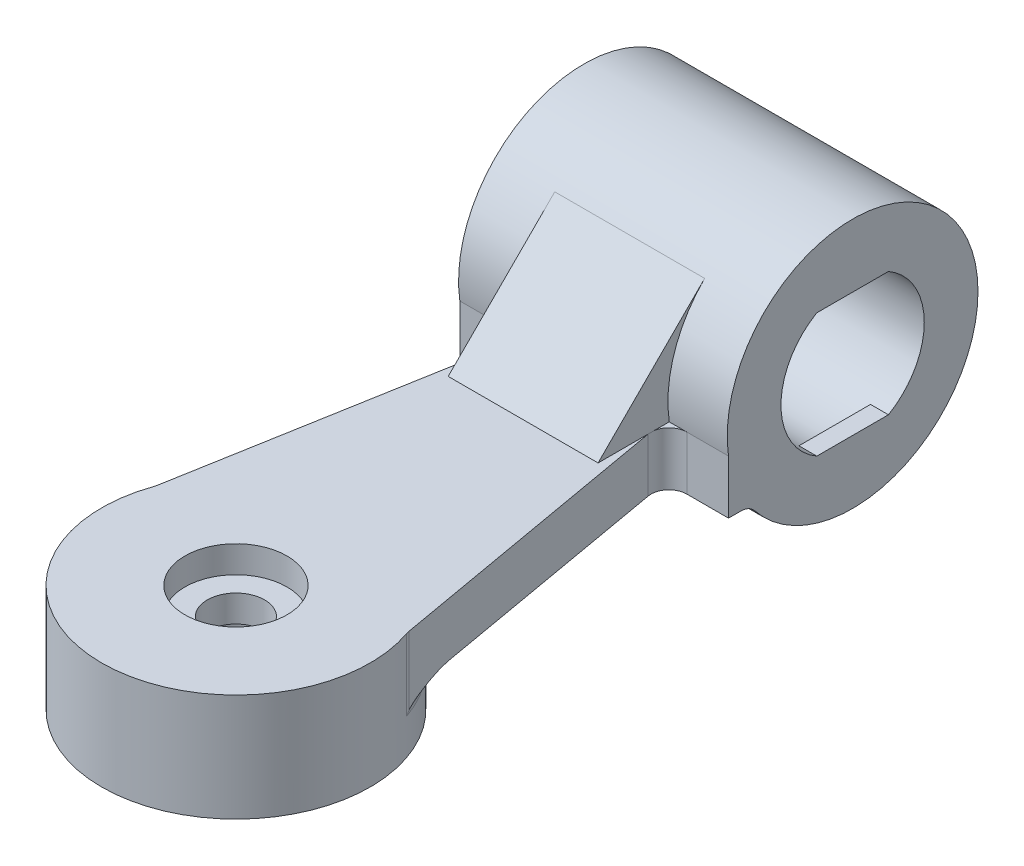
SolidWorks part; units mm, degrees
ref_plane "Front Plane" through (0, 0, 0) normal (0, 0, 1) x (1, 0, 0)
ref_plane "Top Plane" through (0, 0, 0) normal (0, 1, 0) x (1, 0, 0)
ref_plane "Right Plane" through (0, 0, 0) normal (1, 0, 0) x (0, 0, -1)
sketch "Sketch2" plane through (0, 0, 0) normal (0, 1, 0) x (1, 0, 0)
  circle A0 centre (0, 0) radius 7.5
  dimension "D1" = 15
extrude "Boss-Extrude2" add sketch "Sketch2" along normal blind 6
sketch "Sketch3" plane through (0, 6, 0) normal (0, 1, 0) x (1, 0, 0)
  line L0 (-7.0477, 2.5652) -> (-3.9735, 20)
  line L1 (3.9823, 20) -> (7.065, 2.5172)
  line L2 (-3.9735, 20) -> (3.9823, 20)
  circle A0 centre (0, 0) radius 7.5 construction
  arc A1 (7.065, 2.5172) -> (-7.0477, 2.5652) centre (0, 0) ccw
  point P3 (3.9735, 20)
  point P5 (7.065, 2.5652)
  dimension "D1" = 20
  dimension "D2" = 100
  dimension "D3" = 100
extrude "Boss-Extrude3" add sketch "Sketch3" against normal offset from surface (3 mm away) 3 up to face at (0, 0, 7.5)
sketch "Sketch6" plane through (0, 0, 0) normal (0, -1, 0) x (1, 0, 0)
  circle A0 centre (0, 0) radius 2.85
  dimension "D1" = 5.7
extrude "Cut-Extrude1" cut sketch "Sketch6" against normal up to surface (6 mm away) up to face at (-0.002, 6, -8.7603)
sketch "Sketch8" plane through (0, 0, 0) normal (1, 0, 0) x (0, 0, -1)
  line L0 (-7.5, 0) -> (7.5, 0) construction
  circle A0 centre (26.9282, 7) radius 4
  circle A1 centre (26.9282, 7) radius 7
  point P0 (27.3813, 7.7366)
  dimension "D1" = 8
  dimension "D2" = 3
extrude "Boss-Extrude4" add sketch "Sketch8" along normal blind 7.5 and the other way blind 7.5 separate body
sketch "Sketch9" plane through (0, 0, 0) normal (1, 0, 0) x (0, 0, -1)
  line L0 (20, 3) -> (20, 6) construction
  line L1 (20, 3) -> (20, 6)
  line L2 (20, 3) -> (21.1836, 3)
  circle A0 centre (26.9282, 7) radius 7 construction
  arc A1 (20, 6) -> (21.1836, 3) centre (26.9282, 7) ccw
extrude "Boss-Extrude5" add sketch "Sketch9" along normal blind 7.5 and the other way blind 7.5
ref_plane "Plane1" through (0, 3, 0) normal (0, 1, 0) x (1, 0, 0)
sketch "Sketch11" plane through (0, 3, 0) normal (0, 1, 0) x (1, 0, 0)
  circle A0 centre (0, 0) radius 1.6
  circle A1 centre (0, 0) radius 2.85 construction
  circle A2 centre (0, 0) radius 2.85
  dimension "D1" = 3.2
extrude "Boss-Extrude6" add sketch "Sketch11" along normal blind 1.5
fillet "Fillet15" radius 1 2 edges at (3.9823, 4.5, -20) (-3.9735, 4.5, -20)
fillet "Fillet16" radius 1 1 edges at (0, 3, -21.1836)
fillet "Fillet23" radius 1 1 edges at (0.0255, 3, -7.5)
fillet "Fillet24" radius 1 2 edges at (7.065, 4, -2.5172) (-7.0477, 4, -2.5652)
sketch "Sketch12" plane through (7.5, 0, 0) normal (1, 0, 0) x (0, 0, -1)
  line L0 (24.9282, 3.5359) -> (28.9282, 3.5359)
  line L1 (24.9282, 10.4641) -> (28.9282, 10.4641)
  circle A0 centre (26.9282, 7) radius 4 construction
  arc A1 (24.9282, 3.5359) -> (28.9282, 3.5359) centre (26.9282, 7) ccw
  arc A2 (28.9282, 10.4641) -> (24.9282, 10.4641) centre (26.9282, 7) ccw
  dimension "D1" = 4
  dimension "D2" = 4
extrude "Boss-Extrude7" add sketch "Sketch12" against normal blind 1
sketch "Sketch13" plane through (0, 0, 0) normal (1, 0, 0) x (0, 0, -1)
  line L0 (2.5974, 6) -> (18.8264, 6) construction
  line L1 (20, 6) -> (18.8264, 6) construction
  line L2 (16.0287, 6) -> (18.8264, 6)
  line L3 (20, 6) -> (18.8264, 6)
  line L4 (21.9785, 11.9497) -> (16.0287, 6)
  arc A0 (21.4638, 2.625) -> (20, 6) centre (26.9282, 7) ccw construction
  arc A1 (21.9785, 11.9497) -> (20, 6) centre (26.9282, 7) ccw
  dimension "D1" = 45
extrude "Boss-Extrude8" add sketch "Sketch13" along normal up to vertex (4.1892 mm away) and the other way up to vertex (4.1804 mm away) up to point (4.1892, 6, -18.8263) other way up to point (-4.1804, 6, -18.8263)
